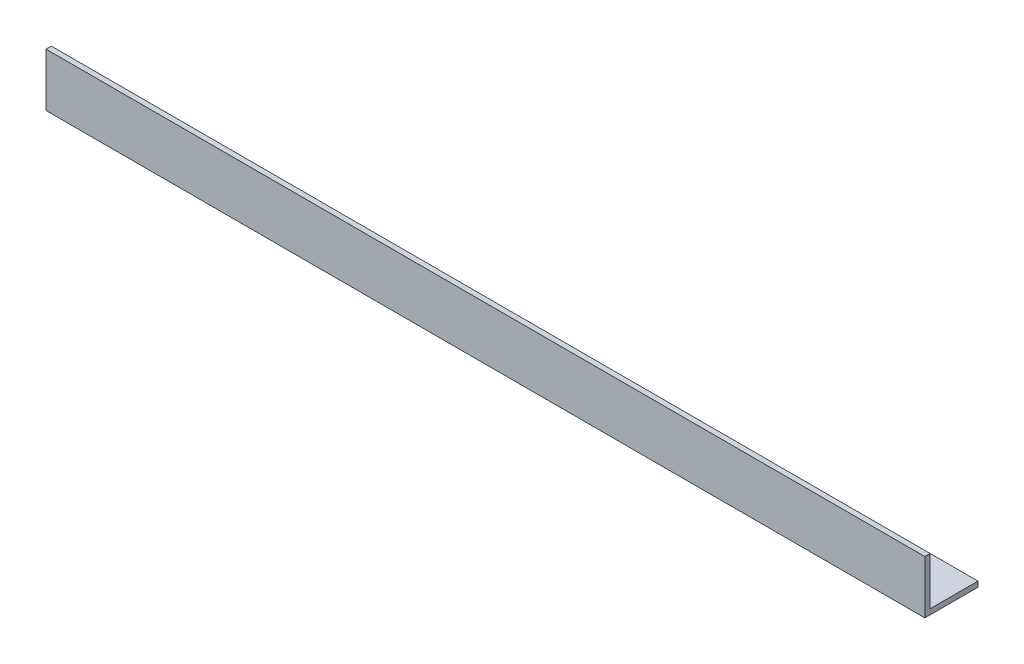
SolidWorks part; units mm, degrees
ref_plane "Спереди" through (0, 0, 0) normal (0, 0, 1) x (1, 0, 0)
ref_plane "Сверху" through (0, 0, 0) normal (0, 1, 0) x (1, 0, 0)
ref_plane "Справа" through (0, 0, 0) normal (1, 0, 0) x (0, 0, -1)
sketch "Эскиз1" plane through (0, 0, 0) normal (1, 0, 0) x (0, 0, -1)
  line L0 (0, 0) -> (30, 0)
  line L1 (0, 0) -> (0, 30)
extrude "Вытянуть-Тонкостенный1" add sketch "Эскиз1" along normal blind 496 thin thin type one direction wall 3
